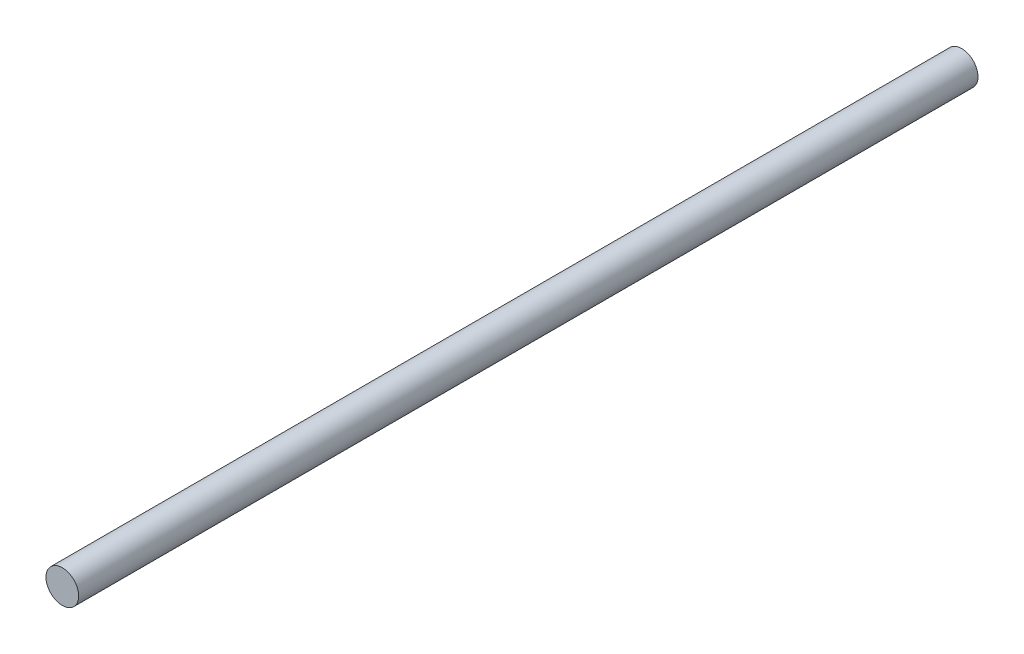
SolidWorks part; units mm, degrees
ref_plane "Ebene vorne" through (0, 0, 0) normal (0, 0, 1) x (1, 0, 0)
ref_plane "Ebene oben" through (0, 0, 0) normal (0, 1, 0) x (1, 0, 0)
ref_plane "Ebene rechts" through (0, 0, 0) normal (1, 0, 0) x (0, 0, -1)
sketch "Skizze1" plane through (0, 0, 0) normal (0, 0, 1) x (1, 0, 0)
  circle A0 centre (0, 0) radius 4
  dimension "D1" = 8
extrude "Aufsatz-Linear austragen1" add sketch "Skizze1" along normal blind 220
